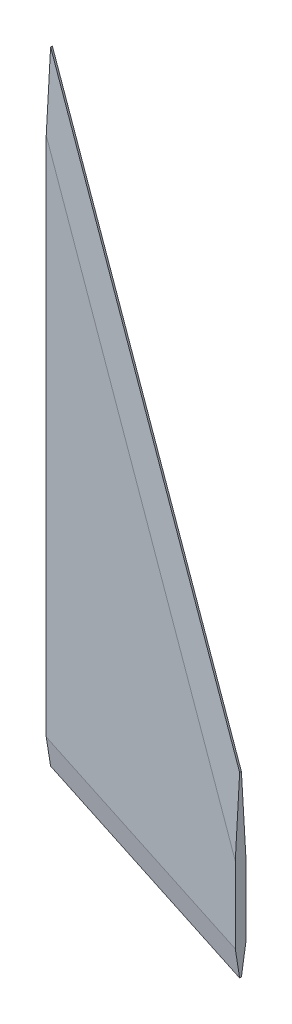
SolidWorks part; units mm, degrees
material "Hexcel AS4C (3000 Filaments)"
ref_plane "Front Plane" through (0, 0, 0) normal (0, 0, 1) x (1, 0, 0)
ref_plane "Top Plane" through (0, 0, 0) normal (0, 1, 0) x (1, 0, 0)
ref_plane "Right Plane" through (0, 0, 0) normal (1, 0, 0) x (0, 0, -1)
sketch "Sketch1" plane through (0, 0, 0) normal (0, 0, 1) x (1, 0, 0)
  line L0 (-16.41, 1.3153) -> (-16.41, 179.1153)
  line L1 (-16.41, 179.1153) -> (37.565, 26.7153)
  line L2 (37.565, 26.7153) -> (37.565, -24.0847)
  line L3 (37.565, -24.0847) -> (-16.41, 1.3153)
  point P2 (0, 0)
  point P5 (-16.41, 1.3153)
  point P7 (-16.41, 179.1153)
  point P9 (37.565, 26.7153)
  point P11 (37.565, -24.0847)
extrude "Boss-Extrude1" add sketch "Sketch1" along normal mid plane 3
chamfer "Chamfer1" distance 1.25 angle 80 4 edges at (10.5775, -11.3847, -1.5) (10.5775, -11.3847, 1.5) (10.5775, 102.9153, -1.5) (10.5775, 102.9153, 1.5) first distance on face at (10.5775, -11.3847, 0) first distance on face at (10.5775, 102.9153, 0)
